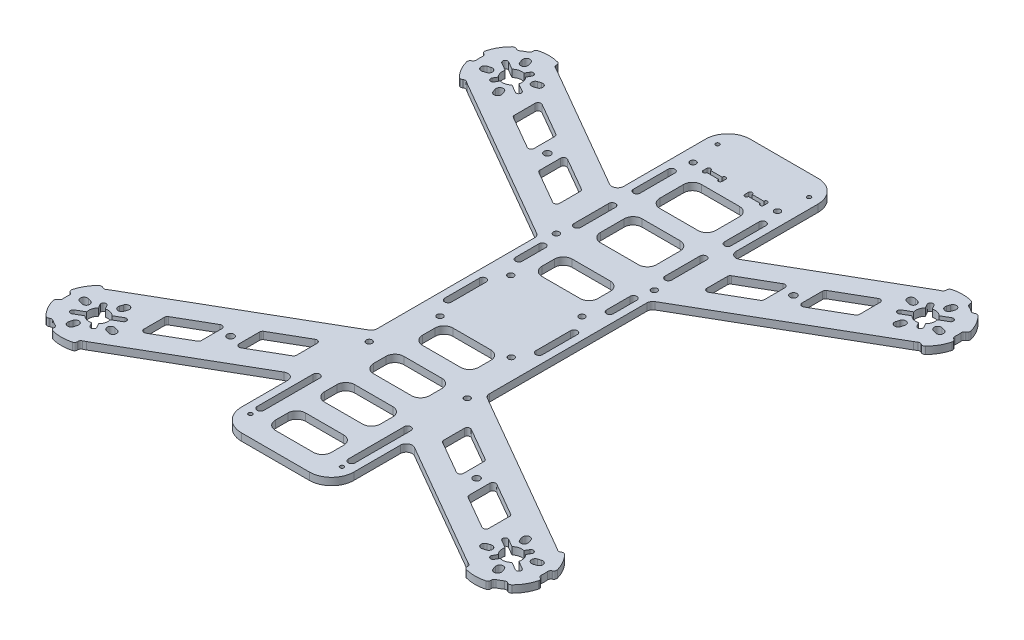
SolidWorks part; units mm, degrees
material "Thornel Mat VMA"
ref_plane "Front Plane" through (0, 0, 0) normal (0, 0, 1) x (1, 0, 0)
ref_plane "Top Plane" through (0, 0, 0) normal (0, 1, 0) x (1, 0, 0)
ref_plane "Right Plane" through (0, 0, 0) normal (1, 0, 0) x (0, 0, -1)
sketch "Sketch1" plane through (0, 0, 0) normal (0, 1, 0) x (1, 0, 0)
  line L1 (-14.5161, 15.7734) -> (14.5161, 15.7734)
  line L2 (-24.0411, 6.2484) -> (-24.0411, -192.1891)
  line L3 (-14.5161, -201.7141) -> (14.5161, -201.7141)
  line L4 (24.0411, 6.2484) -> (24.0411, -192.1891)
  line L7 (0, -201.7141) -> (0, 0) construction
  line L8 (-20.955, -60.6425) -> (20.955, -60.6425) construction
  line L9 (-18.034, -5.08) -> (18.034, -5.08) construction
  line L10 (-20.955, -140.6398) -> (20.955, -140.6398) construction
  arc A0 (24.0411, -192.1891) -> (14.5161, -201.7141) centre (14.5161, -192.1891) cw
  arc A1 (-14.5161, -201.7141) -> (-24.0411, -192.1891) centre (-14.5161, -192.1891) cw
  circle A2 centre (-20.955, -60.6425) radius 1.27
  circle A3 centre (20.955, -60.6425) radius 1.27
  circle A4 centre (-18.034, -5.08) radius 1.27
  circle A5 centre (18.034, -5.08) radius 1.27
  circle A8 centre (-20.955, -140.6398) radius 1.27
  circle A9 centre (20.955, -140.6398) radius 1.27
  arc A10 (24.0411, 6.2484) -> (14.5161, 15.7734) centre (14.5161, 6.2484) ccw
  arc A11 (-14.5161, 15.7734) -> (-24.0411, 6.2484) centre (-14.5161, 6.2484) ccw
  point P7 (24.0411, -201.7141)
  point P13 (-24.0411, -201.7141)
  point P15 (0, -60.6425)
  point P23 (0, -5.08)
  point P28 (0, -140.6398)
  point P35 (-24.0411, 15.7734)
  dimension "D7" = 41.91
  dimension "D10" = 2.54
  dimension "D12" = 9.525
  dimension "D1" = 217.4875
  dimension "D2" = 48.0822
  dimension "D3" = 55.5625
  dimension "D4" = 5.08
  dimension "D5" = 20.8534
  dimension "D8" = 36.068
  dimension "D14" = 79.9973
extrude "MAIN BODY" add sketch "Sketch1" along normal blind 3.1242 contours L1 A11 L2 L3 L4 A10 A5 A4 | L2 A2 | L2 | L4 | L4 A3 | L2 A8 | L2 | L4 A9 | L4 region at (0, 0, 93.0414)
sketch "Sketch2" plane through (0, 3.1242, 0) normal (0, 1, 0) x (1, 0, 0)
  line L0 (8.89, -5.08) -> (8.89, -8.9269) construction
  line L6 (-18.034, -5.08) -> (18.034, -5.08) construction
  line L8 (4.826, -4.2863) -> (12.954, -4.2863)
  line L9 (4.826, -4.2863) -> (4.826, -5.8738)
  line L10 (4.826, -5.8738) -> (12.954, -5.8738)
  line L11 (12.954, -4.2863) -> (12.954, -5.8738)
  line L12 (4.826, -4.2863) -> (12.954, -5.8738) construction
  line L13 (4.826, -5.8738) -> (12.954, -4.2863) construction
  line L14 (0, -201.7141) -> (0, 0) construction
  line L15 (0, -201.7141) -> (0, 0) construction
  circle A0 centre (5.6197, -5.8738) radius 0.7937
  circle A1 centre (5.6197, -4.2863) radius 0.7937
  circle A2 centre (12.1602, -4.2863) radius 0.7937
  circle A3 centre (12.1602, -5.8738) radius 0.7937
  point P3 (8.89, -5.08)
  dimension "D6" = 1.5875
  dimension "D1" = 8.128
  dimension "D2" = 1.5875
  dimension "D3" = 8.89
extrude "CAMERA PLATE SLOTS" cut sketch "Sketch2" against normal through all contours A3 | A2 | L8 L11 L10 L9 | A1 | A0
mirror "Mirror2" about plane through (0, 0, 0) normal (1, 0, 0) of "CAMERA PLATE SLOTS"
sketch "Sketch4" plane through (0, 3.1242, 0) normal (0, 1, 0) x (1, 0, 0)
  line L0 (19.4691, -12.8778) -> (19.4691, -27.7622) construction
  line L1 (20.9169, -12.8778) -> (20.9169, -27.7622)
  line L2 (18.0213, -12.8778) -> (18.0213, -27.7622)
  line L3 (24.0411, 6.2484) -> (24.0411, -192.1891) construction
  arc A0 (20.9169, -12.8778) -> (18.0213, -12.8778) centre (19.4691, -12.8778) ccw
  arc A1 (18.0213, -27.7622) -> (20.9169, -27.7622) centre (19.4691, -27.7622) ccw
  point P2 (19.4691, -20.32)
  dimension "D1" = 2.8956
  dimension "D2" = 17.78
  dimension "D3" = 3.1242
  dimension "D5" = 11.43
extrude "LONG SLOT CUTOUT" cut sketch "Sketch4" against normal through all contours L2 A1 L1 A0
mirror "Mirror1" about plane through (0, 0, 0) normal (1, 0, 0) of "LONG SLOT CUTOUT"
sketch "Sketch3" plane through (0, 3.1242, 0) normal (0, 1, 0) x (1, 0, 0)
  line L0 (0, -201.7141) -> (0, 0) construction
  line L1 (-8.1407, -29.21) -> (8.1407, -29.21)
  line L2 (-11.9507, -25.4) -> (-11.9507, -15.24)
  line L3 (-8.1407, -11.43) -> (8.1407, -11.43)
  line L4 (11.9507, -25.4) -> (11.9507, -15.24)
  line L5 (-11.9507, -29.21) -> (11.9507, -11.43) construction
  line L6 (-11.9507, -11.43) -> (11.9507, -29.21) construction
  arc A0 (-11.9507, -25.4) -> (-8.1407, -29.21) centre (-8.1407, -25.4) ccw
  arc A1 (8.1407, -29.21) -> (11.9507, -25.4) centre (8.1407, -25.4) ccw
  arc A2 (11.9507, -15.24) -> (8.1407, -11.43) centre (8.1407, -15.24) ccw
  arc A3 (-8.1407, -11.43) -> (-11.9507, -15.24) centre (-8.1407, -15.24) ccw
  point P0 (0, -20.32)
  dimension "D1" = 17.78
  dimension "D2" = 23.9014
  dimension "D3" = 11.43
extrude "RECTANGLE CUTOUT" cut sketch "Sketch3" against normal through all
pattern_linear "LPattern1" count 2 spacing 25.4 along (0, 0, 1) of "LONG SLOT CUTOUT", "Mirror1", "RECTANGLE CUTOUT"
pattern_linear "LPattern2" count 2 spacing 80.645 along (0, 0, 1) of "LONG SLOT CUTOUT", "Mirror1"
sketch "Sketch7" plane through (0, 3.1242, 0) normal (0, 1, 0) x (1, 0, 0)
  line L0 (-11.9507, -40.64) -> (-11.9507, -50.8) construction
  line L1 (-8.1407, -66.675) -> (8.1407, -66.675)
  line L2 (-11.9507, -70.485) -> (-11.9507, -75.7936)
  line L3 (-8.1407, -79.6036) -> (8.1407, -79.6036)
  line L4 (11.9507, -70.485) -> (11.9507, -75.7936)
  line L5 (11.9507, -50.8) -> (11.9507, -40.64) construction
  line L6 (-20.955, -60.6425) -> (20.955, -60.6425) construction
  line L7 (-20.955, -60.6425) -> (20.955, -60.6425) construction
  line L8 (-8.1407, -54.61) -> (8.1407, -54.61) construction
  arc A0 (-11.9507, -75.7936) -> (-8.1407, -79.6036) centre (-8.1407, -75.7936) ccw
  arc A1 (11.9507, -75.7936) -> (8.1407, -79.6036) centre (8.1407, -75.7936) cw
  arc A2 (11.9507, -70.485) -> (8.1407, -66.675) centre (8.1407, -70.485) ccw
  arc A3 (-8.1407, -66.675) -> (-11.9507, -70.485) centre (-8.1407, -70.485) ccw
  dimension "D1" = 3.81
  dimension "D2" = 12.9286
extrude "Cut-Extrude5" cut sketch "Sketch7" against normal through all
sketch "Sketch8" plane through (0, 3.1242, 0) normal (0, 1, 0) x (1, 0, 0)
  line L0 (19.4691, -68.1228) -> (19.4691, -78.1558) construction
  line L1 (20.9169, -68.1228) -> (20.9169, -78.1558)
  line L2 (18.0213, -68.1228) -> (18.0213, -78.1558)
  line L3 (19.4691, -12.8778) -> (19.4691, -27.7622) construction
  line L4 (18.0213, -12.8778) -> (18.0213, -27.7622) construction
  line L5 (8.1407, -66.675) -> (-8.1407, -66.675) construction
  line L6 (-8.1407, -79.6036) -> (8.1407, -79.6036) construction
  arc A0 (20.9169, -68.1228) -> (18.0213, -68.1228) centre (19.4691, -68.1228) ccw
  arc A1 (18.0213, -78.1558) -> (20.9169, -78.1558) centre (19.4691, -78.1558) ccw
  point P2 (19.4691, -73.1393)
extrude "Cut-Extrude6" cut sketch "Sketch8" against normal through all
mirror "Mirror4" about plane through (0, 0, 0) normal (1, 0, 0) of "Cut-Extrude6"
sketch "CC3D HOLE SYM SKETCH" plane through (0, 3.1242, 0) normal (0, 1, 0) x (1, 0, 0)
  line L0 (19.4691, -78.1558) -> (19.4691, -93.5228) construction
  line L1 (19.4691, -85.8393) -> (32.4524, -85.8393) construction
  line L2 (19.4691, -93.5228) -> (19.4691, -108.4072) construction
  line L3 (19.4691, -100.965) -> (32.4524, -100.965) construction
ref_plane "CC3D 1ST PAIR HOLES" through (0, 0, 85.8393) normal (0, 0, 1) x (1, 0, 0)
ref_plane "CC3D 2ND PAIR HOLES MIRROR PLANE" through (0, 0, 100.965) normal (0, 0, 1) x (1, 0, 0)
sketch "Sketch10" plane through (0, 3.1242, 0) normal (0, 1, 0) x (1, 0, 0)
  line L0 (-1.7183, -85.8393) -> (1.7183, -85.8393) construction
  line L1 (0, -201.7141) -> (0, 0) construction
  line L2 (0, -201.7141) -> (0, 0) construction
  circle A0 centre (15.24, -85.8393) radius 1.27
  circle A1 centre (-15.24, -85.8393) radius 1.27
  dimension "D1" = 2.54
  dimension "D2" = 30.48
extrude "CC3D 1ST PAIR HOLES CUT" cut sketch "Sketch10" against normal through all
mirror "CC3D 2ND PAIR HOLES MIRROR" about plane through (0, 0, 100.965) normal (0, 0, 1) of "CC3D 1ST PAIR HOLES CUT"
pattern_linear "LPattern11" count 2 spacing 51.0286 along (0, 0, 1) of "Cut-Extrude5"
pattern_linear "LPattern13" count 4 spacing 20.9804 along (0, 0, 1) of face at (10.4402, 1.5621, 129.1217) of face at (11.9507, 1.5621, 124.1679) of face at (0, 1.5621, 130.6322) of face at (-10.4402, 1.5621, 129.1217) of face at (-11.9507, 1.5621, 124.1679) of face at (-10.4402, 1.5621, 119.2141) of face at (0, 1.5621, 117.7036) of face at (10.4402, 1.5621, 119.2141)
sketch "Sketch11" plane through (0, 3.1242, 0) normal (0, 1, 0) x (1, 0, 0)
  line L0 (19.4691, -164.6682) -> (19.4691, -188.5696) construction
  line L1 (20.9169, -164.6682) -> (20.9169, -188.5696)
  line L2 (18.0213, -164.6682) -> (18.0213, -188.5696)
  line L3 (19.4691, -12.8778) -> (19.4691, -27.7622) construction
  line L4 (18.0213, -12.8778) -> (18.0213, -27.7622) construction
  line L5 (8.1407, -168.783) -> (8.1407, -184.4548) construction
  arc A0 (20.9169, -164.6682) -> (18.0213, -164.6682) centre (19.4691, -164.6682) ccw
  arc A1 (18.0213, -188.5696) -> (20.9169, -188.5696) centre (19.4691, -188.5696) ccw
  point P2 (19.4691, -176.6189)
  point P15 (8.1407, -176.6189)
  dimension "D1" = 26.797
extrude "Cut-Extrude8" cut sketch "Sketch11" against normal through all
mirror "Mirror6" about plane through (0, 0, 0) normal (1, 0, 0) of "Cut-Extrude8"
sketch "Sketch12" plane through (0, 3.1242, 0) normal (0, 1, 0) x (1, 0, 0)
  line L0 (-19.558, 6.8834) -> (19.558, 6.8834) construction
  line L1 (0, -201.7141) -> (0, 0) construction
  line L2 (-14.5161, 15.7734) -> (14.5161, 15.7734) construction
  circle A0 centre (19.558, 6.8834) radius 0.8255
  circle A1 centre (-19.558, 6.8834) radius 0.8255
  point P2 (0, 6.8834)
  dimension "D2" = 1.651
  dimension "D1" = 8.89
  dimension "D3" = 39.116
extrude "Cut-Extrude9" cut sketch "Sketch12" against normal through all
ref_plane "CNTR OF LENGTH PLANE" through (0, 0, 92.9704) normal (0, 0, 1) x (1, 0, 0)
mirror "Mirror7" about plane through (0, 0, 92.9704) normal (0, 0, 1) of "Cut-Extrude9"
sketch "Sketch13" plane through (0, 3.1242, 0) normal (0, 1, 0) x (1, 0, 0)
  line L0 (88.3883, -12.1666) -> (17.0561, -53.3503) construction
  line L1 (17.0561, -53.3503) -> (88.3883, -53.3503) construction
  line L2 (10.0711, -41.2519) -> (81.4033, -0.0682)
  line L3 (24.0411, -65.4487) -> (95.3733, -24.265)
  line L4 (81.5143, -16.1353) -> (95.2624, -8.1979) construction
  line L5 (80.9745, -15.2005) -> (94.7227, -7.263)
  line L6 (82.054, -17.0702) -> (95.8022, -9.1327)
  line L7 (85.4356, -7.0523) -> (91.3411, -17.2809) construction
  line L8 (86.3705, -6.5125) -> (92.276, -16.7412)
  line L9 (84.5007, -7.592) -> (90.4062, -17.8207)
  line L10 (10.0711, -41.2519) -> (24.0411, -65.4487)
  line L11 (-14.5161, 15.7734) -> (14.5161, 15.7734) construction
  line L12 (-88.3883, -12.1666) -> (88.3883, -12.1666) construction
  line L13 (-88.3883, -12.1666) -> (-88.3883, -188.9433) construction
  line L14 (-88.3883, -188.9433) -> (88.3883, -188.9433) construction
  line L15 (88.3883, -12.1666) -> (88.3883, -188.9433) construction
  line L16 (24.0411, 6.2484) -> (24.0411, -192.1891) construction
  line L17 (24.0411, 6.2484) -> (24.0411, -192.1891)
  line L18 (-88.3883, -100.5549) -> (88.3883, -100.5549) construction
  circle A0 centre (88.3883, -12.1666) radius 4.1275
  circle A1 centre (88.3883, -12.1666) radius 13.97
  arc A2 (80.9745, -15.2005) -> (82.054, -17.0702) centre (81.5143, -16.1353) ccw
  arc A3 (95.8022, -9.1327) -> (94.7227, -7.263) centre (95.2624, -8.1979) ccw
  arc A4 (86.3705, -6.5125) -> (84.5007, -7.592) centre (85.4356, -7.0523) ccw
  arc A5 (90.4062, -17.8207) -> (92.276, -16.7412) centre (91.3411, -17.2809) ccw
  point P11 (88.3883, -12.1666)
  point P16 (88.3883, -12.1666)
  point P27 (0, -12.1666)
  dimension "D3" = 27.94
  dimension "D4" = 8.255
  dimension "D5" = 15.875
  dimension "D8" = 11.811
  dimension "D1" = 30
  dimension "D2" = 27.94
  dimension "D6" = 2.159
  dimension "D7" = 2.159
  dimension "D9" = 176.7767
  dimension "D10" = 250
  dimension "D12" = 176.7767
  dimension "D13" = 27.94
extrude "MOTOR ARM" add sketch "Sketch13" against normal through all separate body contours A1 L2 L17 L3 | A1 A5 L9 A0 L6 A2 L5 A4 L8 A3 region at (51.6784, 3.1242, 34.0459) region at (95.1758, 3.1242, 0.4104)
ref_plane "FWD-AFT MOTOR SPAN CNTR PLANE" through (0, 0, 100.5549) normal (0, 0, 1) x (1, 0, 0)
sketch "Sketch14" plane through (0, 3.1242, 0) normal (0, 1, 0) x (1, 0, 0)
  line L0 (97.1185, -1.2604) -> (98.8736, -0.2471)
  line L1 (102.1985, -10.0592) -> (103.9536, -9.0459)
  line L2 (88.3883, -12.1666) -> (17.0561, -53.3503) construction
  line L3 (88.3883, -12.1666) -> (17.0561, -53.3503) construction
  circle A0 centre (88.3883, -12.1666) radius 15.875
  circle A2 centre (88.3883, -12.1666) radius 13.97 construction
  circle A3 centre (88.3883, -12.1666) radius 13.97
  dimension "D2" = 31.75
  dimension "D1" = 10.16
extrude "Boss-Extrude2" add sketch "Sketch14" against normal through all contours A3 L1 A0 L0 region at (101.0521, 3.1242, 4.8552)
pattern_circular "CirPattern1" count 6 over 360 about axis through (88.3883, 0, 12.1666) along (0, 1, 0) skipping 2, 3, 4 of "Boss-Extrude2"
sketch "Sketch15" plane through (0, 3.1242, 0) normal (0, 1, 0) x (1, 0, 0)
  line L0 (90.7298, -4.5823) -> (80.6494, -10.4022) construction
  line L1 (90.7298, -4.5823) -> (96.1273, -13.931) construction
  line L2 (80.6494, -10.4022) -> (86.0469, -19.7509) construction
  line L3 (96.1273, -13.931) -> (86.0469, -19.7509) construction
  line L4 (90.7298, -4.5823) -> (86.0469, -19.7509) construction
  line L5 (80.6494, -10.4022) -> (96.1273, -13.931) construction
  line L6 (88.3883, -12.1666) -> (17.0561, -53.3503) construction
  line L7 (91.1418, -3.2475) -> (90.7298, -4.5823) construction
  line L8 (92.598, -3.697) -> (92.1859, -5.0318)
  line L9 (89.6857, -2.7979) -> (89.2736, -4.1327)
  circle A0 centre (88.3883, -12.1666) radius 7.9375 construction
  arc A1 (92.598, -3.697) -> (89.6857, -2.7979) centre (91.1418, -3.2475) ccw
  arc A2 (89.2736, -4.1327) -> (92.1859, -5.0318) centre (90.7298, -4.5823) ccw
  point P1 (88.3883, -12.1666)
  point P12 (90.9358, -3.9149)
  dimension "D2" = 4.445
  dimension "D1" = 3.048
  dimension "D3" = 10.795
extrude "Cut-Extrude10" cut sketch "Sketch15" against normal through all
pattern_circular "CirPattern2" count 4 over 360 about axis through (88.3883, 0, 12.1666) along (0, 1, 0) of "Cut-Extrude10"
fillet "Fillet1" radius 1.27 12 edges at (98.8736, 1.5621, 24.0861) (103.9536, 1.5621, 15.2873) (102.1985, 1.5621, 14.274) (102.1985, 1.5621, 10.0592) (103.9536, 1.5621, 9.0459) (98.8736, 1.5621, 0.2471) (97.1185, 1.5621, 1.2604) (93.4683, 1.5621, -0.847) (93.4683, 1.5621, -2.8737) (83.3083, 1.5621, -2.8737) (83.3083, 1.5621, -0.847) (97.1185, 1.5621, 23.0728)
sketch "Sketch16" plane through (0, 3.1242, 0) normal (0, 1, 0) x (1, 0, 0)
  line L8 (28.4861, -40.8853) -> (85.8483, -7.7672)
  line L9 (31.4579, -39.1695) -> (47.9679, -29.6375)
  line L10 (31.4579, -39.1695) -> (31.4579, -50.9013)
  line L11 (19.5961, -57.7497) -> (90.9283, -16.566)
  line L12 (31.4579, -50.9013) -> (47.9679, -41.3692)
  line L13 (47.9679, -29.6375) -> (47.9679, -41.3692)
  line L14 (57.2389, -24.2849) -> (57.2389, -36.0166)
  line L15 (20.9169, -38.2778) -> (20.9169, -53.1622) construction
  line L16 (73.7489, -14.7528) -> (73.7489, -26.4846)
  line L17 (57.2389, -24.2849) -> (73.7489, -14.7528)
  line L18 (57.2389, -36.0166) -> (73.7489, -26.4846)
  line L19 (88.3883, -12.1666) -> (17.0561, -53.3503) construction
  line L20 (47.9679, -35.5034) -> (52.6034, -32.827) construction
  line L21 (52.6034, -32.827) -> (57.2389, -30.1507) construction
  line L23 (24.0411, 6.2484) -> (24.0411, -192.1891) construction
  circle A0 centre (52.6034, -32.827) radius 1.4605
  arc A2 (79.9188, -7.9569) -> (79.0197, -10.8693) centre (79.4692, -9.4131) ccw construction
  dimension "D5" = 2.921
  dimension "D3" = 10.541
  dimension "D4" = 9.271
  dimension "D6" = 4.6355
  dimension "D7" = 16.51
  dimension "D8" = 4.1963
  dimension "D9" = 28.5623
  dimension "D1" = 8.89
  dimension "D2" = 8.89
extrude "Cut-Extrude11" cut sketch "Sketch16" against normal through all
fillet "Fillet2" radius 1.27 8 edges at (57.2389, 1.5621, 24.2849) (57.2389, 1.5621, 36.0166) (73.7489, 1.5621, 26.4846) (47.9679, 1.5621, 41.3692) (47.9679, 1.5621, 29.6375) (31.4579, 1.5621, 39.1695) (31.4579, 1.5621, 50.9013) (73.7489, 1.5621, 14.7528)
mirror "Mirror24" about plane through (0, 0, 0) normal (1, 0, 0) of bodies 133
mirror "Mirror25" about plane through (0, 0, 100.5549) normal (0, 0, 1) of bodies 133 135
combine bodies "Combine1" operation type add bodies to combine 133 127 135 138 137
fillet "Fillet3" radius 2.54 8 edges at (24.0411, 1.5621, 33.1863) (-24.0411, 1.5621, 33.1863) (-24.0411, 1.5621, 65.4487) (-24.0411, 1.5621, 135.6612) (-24.0411, 1.5621, 167.9236) (24.0411, 1.5621, 167.9236) (24.0411, 1.5621, 135.6612) (24.0411, 1.5621, 65.4487)
